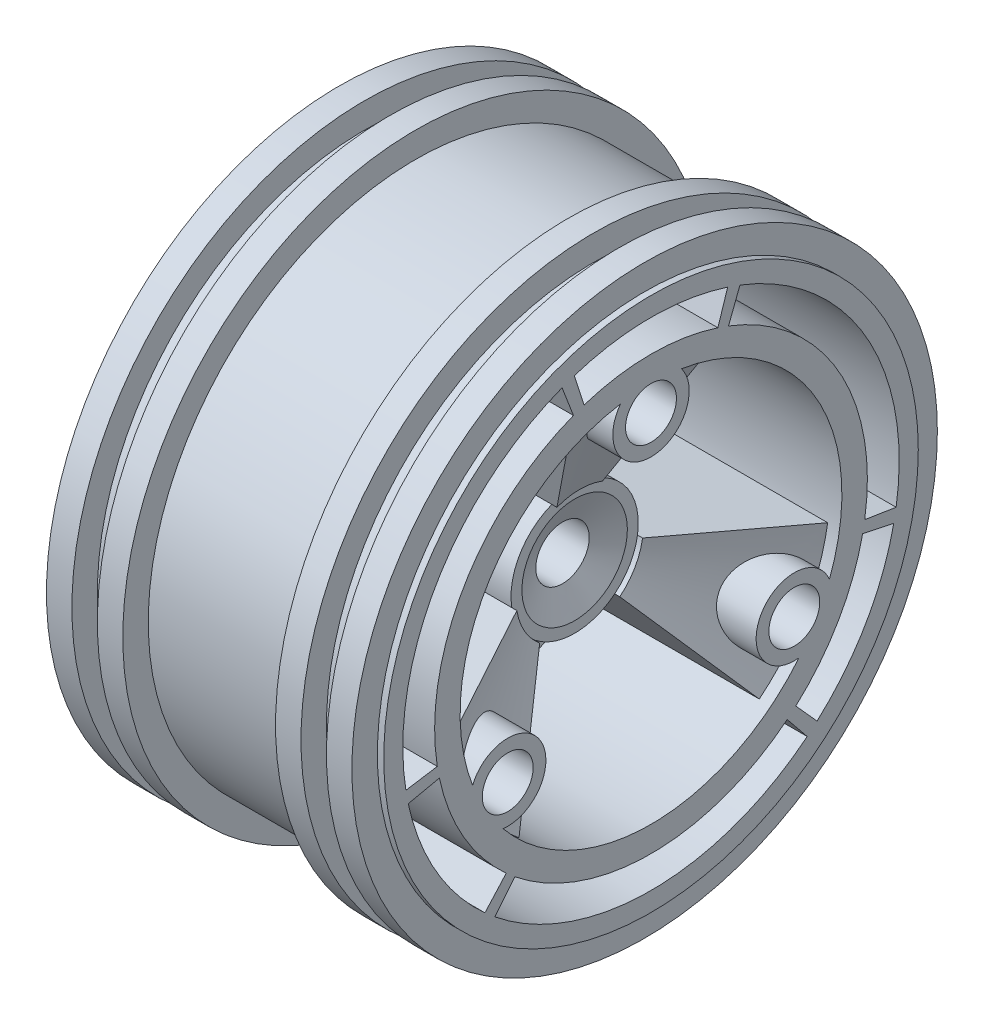
SolidWorks part; units mm, degrees
ref_plane "Plan de face" through (0, 0, 0) normal (0, 0, 1) x (1, 0, 0)
ref_plane "Plan de dessus" through (0, 0, 0) normal (0, 1, 0) x (1, 0, 0)
ref_plane "Plan de droite" through (0, 0, 0) normal (1, 0, 0) x (0, 0, -1)
sketch "Esquisse1" plane through (0, 0, 0) normal (0, 0, 1) x (1, 0, 0)
  line L0 (-6.5, -2) -> (5.5, -2)
  line L1 (-6.5, -2) -> (-6.5, -19)
  line L2 (12.5, -17) -> (5.5, -2)
  line L3 (0, 0) -> (-22.8628, 0) construction
  line L5 (-6.5, -19) -> (-12.5, -19)
  line L6 (12.5, -17) -> (12.5, -21)
  line L7 (-12.5, -19) -> (-12.5, -21)
  line L8 (-12, -23) -> (12, -23) construction
  line L9 (-19.4227, -21) -> (12.5, -21) construction
  line L10 (-12, -23) -> (-10, -23)
  line L11 (-10, -23) -> (-10, -21)
  line L12 (-10, -21) -> (-8, -21)
  line L13 (-8, -21) -> (-8, -23)
  line L14 (-8, -23) -> (-6, -23)
  line L15 (-6, -23) -> (-6, -21)
  line L16 (-6, -21) -> (6, -21)
  line L17 (6, -21) -> (6, -23)
  line L18 (6, -23) -> (8, -23)
  line L19 (8, -23) -> (8, -21)
  line L20 (8, -21) -> (10, -21)
  line L21 (10, -21) -> (10, -23)
  line L22 (10, -23) -> (12, -23)
  line L23 (-12.5, -21) -> (-12, -21)
  line L24 (-12, -21) -> (-12, -23)
  line L25 (12.5, -21) -> (12, -21)
  line L26 (12, -21) -> (12, -23)
  point P0 (0, 0)
  dimension "D1" = 2
  dimension "D2" = 12
  dimension "D3" = 5.5
  dimension "D4" = 23
  dimension "D5" = 23
  dimension "D6" = 15
  dimension "D7" = 6
  dimension "D8" = 4
  dimension "D9" = 25
  dimension "D10" = 2
  dimension "D11" = 0.5
  dimension "D12" = 2
  dimension "D13" = 4
  dimension "D14" = 2
  dimension "D15" = 0.5
  dimension "D16" = 4
  dimension "D17" = 6
  dimension "D18" = 6
revolve "Révolution1" add sketch "Esquisse1" angle 360 about L3
sketch "Esquisse2" plane through (-6.5, 0, 0) normal (-1, 0, 0) x (0, 0, 1)
  line L0 (0, 19) -> (0, 15) construction
  line L1 (-19, 0) -> (-15, 0) construction
  line L2 (-9.5263, 5.5) -> (-8.6603, 5) construction
  line L3 (-9.5263, -5.5) -> (-8.6603, -5) construction
  line L4 (-1.8187, 1.05) -> (1.8187, -1.05) construction
  line L5 (-2.1, 0) -> (5, 0) construction
  line L6 (-1.8187, -1.05) -> (1.8187, 1.05) construction
  line L7 (0, 5) -> (0, -2.1) construction
  line L8 (0, 11) -> (0, 10) construction
  line L9 (8.6603, -5) -> (9.5263, -5.5) construction
  line L10 (15, 0) -> (19, 0) construction
  line L11 (0, -10) -> (0, -11) construction
  line L12 (-5.1303, 14.0954) -> (0, 0) construction
  line L13 (5.1303, 14.0954) -> (0, 0) construction
  line L14 (5.1303, 14.0954) -> (1.7101, 4.6985)
  line L15 (-5.1303, 14.0954) -> (-1.7101, 4.6985)
  line L16 (0, 0) -> (-14.7721, -2.6047) construction
  line L17 (0, 0) -> (-9.6418, -11.4907) construction
  line L18 (0, 0) -> (14.7721, -2.6047) construction
  line L19 (0, 0) -> (9.6418, -11.4907) construction
  line L20 (-14.7721, -2.6047) -> (-4.924, -0.8682)
  line L21 (-9.6418, -11.4907) -> (-3.2139, -3.8302)
  line L22 (9.6418, -11.4907) -> (3.2139, -3.8302)
  line L23 (14.7721, -2.6047) -> (4.924, -0.8682)
  circle A0 centre (-11.2583, 6.5) radius 2
  circle A1 centre (0, 0) radius 2.1
  circle A2 centre (11.2583, -6.5) radius 2
  circle A3 centre (0, 0) radius 19 construction
  circle A4 centre (0, 0) radius 19 construction
  circle A5 centre (0, 13) radius 2
  circle A6 centre (0, -13) radius 2
  arc A7 (-2.3942, 14.8077) -> (-11.6267, 9.4773) centre (0, 0) ccw
  circle A8 centre (-11.2583, -6.5) radius 2
  circle A9 centre (11.2583, 6.5) radius 2
  circle A10 centre (0, 0) radius 5
  arc A11 (-2.3942, 14.8077) -> (2.3942, 14.8077) centre (0, 13) ccw
  arc A12 (11.6267, 9.4773) -> (14.0209, 5.3304) centre (11.2583, 6.5) ccw
  arc A13 (-14.0209, 5.3304) -> (-11.6267, 9.4773) centre (-11.2583, 6.5) ccw
  arc A14 (-11.6267, -9.4773) -> (-14.0209, -5.3304) centre (-11.2583, -6.5) ccw
  arc A15 (2.3942, -14.8077) -> (-2.3942, -14.8077) centre (0, -13) ccw
  arc A16 (14.0209, -5.3304) -> (11.6267, -9.4773) centre (11.2583, -6.5) ccw
  arc A17 (-14.0209, 5.3304) -> (-14.0209, -5.3304) centre (0, 0) ccw
  arc A18 (11.6267, 9.4773) -> (2.3942, 14.8077) centre (0, 0) ccw
  arc A19 (14.0209, -5.3304) -> (14.0209, 5.3304) centre (0, 0) ccw
  arc A20 (2.3942, -14.8077) -> (11.6267, -9.4773) centre (0, 0) ccw
  arc A21 (-11.6267, -9.4773) -> (-2.3942, -14.8077) centre (0, 0) ccw
  circle A22 centre (0, 0) radius 3
  circle M1 centre (0, 0) radius 19
  dimension "D1" = 4.2
  dimension "D2" = 4
  dimension "D3" = 4
  dimension "D8" = 4
  dimension "D9" = 4
  dimension "D10" = 4
  dimension "D11" = 4
  dimension "D16" = 10
  dimension "D17" = 6
  dimension "D18" = 6
  dimension "D19" = 6
  dimension "D20" = 6
  dimension "D21" = 6
  dimension "D22" = 6
  dimension "D29" = 6
  dimension "D4" = 13
  dimension "D5" = 13
  dimension "D6" = 30
  dimension "D7" = 60
  dimension "D12" = 13
  dimension "D13" = 13
  dimension "D14" = 13
  dimension "D15" = 13
  dimension "D23" = 20
  dimension "D24" = 40
  dimension "D25" = 20
  dimension "D26" = 40
  dimension "D27" = 20
  dimension "D28" = 40
extrude "Enlèv. mat.-Extru.1" cut sketch "Esquisse2" against normal blind 20 contours A0 region at (-6.5, 6.5, -11.2583)
extrude "Enlèv. mat.-Extru.2" cut sketch "Esquisse2<3>" against normal blind 20 contours A5 | A9 | A2 | A6 | A8 | A1 region at (-6.5, 0, 0) region at (-6.5, -6.5, 11.2583) region at (-6.5, 13, 0) region at (-6.5, -13, 0) region at (-6.5, -6.5, -11.2583) region at (-6.5, 6.5, 11.2583)
sketch "Esquisse2<3>" plane through (-6.5, 0, 0) normal (-1, 0, 0) x (0, 0, 1) same geometry as "Esquisse2"
extrude "Enlèv. mat.-Extru.3" cut sketch "Esquisse2<4>" against normal blind 11 contours L14 A18 A11 A7 L15 A10 | L22 A20 A16 A19 L23 A10 | A14 A21 L21 A10 L20 A17 region at (-6.5, 9.4701, 0) region at (-6.5, -4.7351, 8.2014) region at (-6.5, -4.7351, -8.2014)
sketch "Esquisse2<4>" plane through (-6.5, 0, 0) normal (-1, 0, 0) x (0, 0, 1) same geometry as "Esquisse2"
extrude "Enlèv. mat.-Extru.4" cut sketch "Esquisse2<6>" against normal blind 1 contours A10 A22 region at (-6.5, 2.7868, 3.9799)
sketch "Esquisse2<6>" plane through (-6.5, 0, 0) normal (-1, 0, 0) x (0, 0, 1) same geometry as "Esquisse2"
extrude "Enlèv. mat.-Extru.5" cut sketch "Esquisse2<7>" against normal blind 0.5 contours A13 A17 L20 A10 L15 A7 | L23 A19 A12 A18 L14 A10 | L21 A21 A15 A20 L22 A10 region at (-6.5, 4.6938, 8.1298) region at (-6.5, 4.6938, -8.1298) region at (-6.5, -9.3875, 0)
sketch "Esquisse2<7>" plane through (-6.5, 0, 0) normal (-1, 0, 0) x (0, 0, 1) same geometry as "Esquisse2"
extrude "Boss.-Extru.1" add sketch "Esquisse2<8>" against normal blind 19 contours A21 A14 A17 A13 A7 A11 A18 A12 A19 A16 A20 A15 A9 A8 A6 A5 A2 A0 M1 region at (-6.5, 0, -18.4626)
sketch "Esquisse2<8>" plane through (-6.5, 0, 0) normal (-1, 0, 0) x (0, 0, 1) same geometry as "Esquisse2"
sketch "Esquisse7" plane through (12.5, 0, 0) normal (1, 0, 0) x (0, 0, -1)
  line L0 (0, 15) -> (0, -15) construction
  line L1 (-4.5925, -1.9771) -> (14.8691, -1.9771) construction
  line L2 (-5.3755, 14.0037) -> (-1.1227, 2.9248) construction
  line L3 (0, 0) -> (1.0751, 2.8007) construction
  line L4 (-5.3755, 14.0037) -> (-1.1227, 2.9248)
  line L5 (5.3755, 14.0037) -> (1.7918, 4.6679)
  line L6 (-14.8153, -2.3465) -> (-4.9384, -0.7822) construction
  line L7 (0, 0) -> (-1.888, -2.3314) construction
  line L8 (9.4398, -11.6572) -> (1.888, -2.3314) construction
  line L9 (0, 0) -> (2.9631, -0.4693) construction
  line L10 (14.8153, -2.3465) -> (4.9384, -0.7822)
  line L11 (9.4398, -11.6572) -> (1.888, -2.3314)
  line L12 (1.888, -2.3314) -> (0, 0) construction
  line L13 (4.9384, -0.7822) -> (14.8153, -2.3465) construction
  line L14 (1.7918, 4.6679) -> (5.3755, 14.0037) construction
  line L15 (-1.0751, 2.8007) -> (0, 0) construction
  line L16 (-2.9631, -0.4693) -> (0, 0) construction
  line L17 (-3.1466, -3.8857) -> (-9.4398, -11.6572) construction
  line L18 (-14.8153, -2.3465) -> (-4.9384, -0.7822)
  line L19 (-9.4398, -11.6572) -> (-3.1466, -3.8857)
  circle A0 centre (0, 13) radius 2 construction
  circle A1 centre (0, -13) radius 2 construction
  arc A2 (2.3942, -14.8077) -> (-2.3942, -14.8077) centre (0, -13) ccw
  circle A4 centre (0, 0) radius 5
  circle A5 centre (0, 0) radius 3
  arc A6 (2.3942, -14.8077) -> (14.0209, 5.3304) centre (0, 0) ccw
  arc A7 (-14.0209, 5.3304) -> (-11.6267, 9.4773) centre (-11.2583, 6.5) ccw
  arc A8 (11.6267, 9.4773) -> (14.0209, 5.3304) centre (11.2583, 6.5) ccw
  arc A9 (-14.8153, -2.3465) -> (-2.3942, -14.8077) centre (0, 0) ccw
  arc A10 (11.6267, 9.4773) -> (-11.6267, 9.4773) centre (0, 0) ccw
  circle A11 centre (0, 0) radius 15
  arc M1 (-14.0209, 5.3304) -> (-11.6267, 9.4773) centre (-11.2583, 6.5) ccw
  arc M5 (11.6267, 9.4773) -> (14.0209, 5.3304) centre (11.2583, 6.5) ccw
  arc M9 (2.3942, -14.8077) -> (-2.3942, -14.8077) centre (0, -13) ccw
  dimension "D1" = 10
  dimension "D2" = 6
  dimension "D3" = 30
  dimension "D10" = 6
  dimension "D11" = 6
  dimension "D12" = 6
  dimension "D4" = 69
  dimension "D5" = 69
  dimension "D6" = 9
  dimension "D7" = 42
  dimension "D8" = 9
  dimension "D9" = 42
extrude "Enlèv. mat.-Extru.6" cut sketch "Esquisse7" against normal blind 15 contours A4 L19 L11 M9 | A4 L4 L18 M1 | A4 L10 L5 M5 region at (12.5, 4.7099, 8.1578) region at (12.5, 4.7099, -8.1578) region at (12.5, -9.4198, 0)
extrude "Enlèv. mat.-Extru.9" cut sketch "Esquisse7<5>" against normal blind 6 contours A4 A5 region at (12.5, 4.8586, 0)
sketch "Esquisse7<5>" plane through (12.5, 0, 0) normal (1, 0, 0) x (0, 0, -1) same geometry as "Esquisse7"
sketch "Esquisse13" plane through (12.5, 0, 0) normal (1, 0, 0) x (0, 0, -1)
  arc A0 (11.6267, 9.4773) -> (14.0209, 5.3304) centre (11.2583, 6.5) ccw
  arc A1 (-14.0209, 5.3304) -> (-11.6267, 9.4773) centre (-11.2583, 6.5) ccw
  arc A2 (2.3942, -14.8077) -> (-2.3942, -14.8077) centre (0, -13) ccw
  arc A3 (-11.6267, 9.4773) -> (-14.0209, 5.3304) centre (0, 0) ccw
  arc A4 (-2.3942, -14.8077) -> (2.3942, -14.8077) centre (0, 0) ccw
  arc A5 (14.0209, 5.3304) -> (11.6267, 9.4773) centre (0, 0) ccw
  dimension "D1" = 30
  dimension "D2" = 6
  dimension "D3" = 6
  dimension "D4" = 6
extrude "Enlèv. mat.-Extru.12" cut sketch "Esquisse13" against normal blind 14.5
sketch "Esquisse14" plane through (12.5, 0, 0) normal (1, 0, 0) x (0, 0, -1)
  line L0 (0, -17) -> (0, 15) construction
  line L1 (-14.8661, 0) -> (14.8661, 0) construction
  line L2 (6.0923, 15.8709) -> (6.9882, 18.2048)
  line L3 (-6.0923, 15.8709) -> (-6.9882, 18.2048)
  line L4 (-19.2599, -3.0505) -> (-16.7907, -2.6594)
  line L5 (-10.6984, -13.2115) -> (-12.2717, -15.1543)
  line L6 (12.2717, -15.1543) -> (10.6984, -13.2115)
  line L7 (16.7907, -2.6594) -> (19.2599, -3.0505)
  line L8 (5.2533, 16.168) -> (6.0258, 18.5456)
  line L9 (-6.0258, 18.5456) -> (-5.2533, 16.168)
  line L10 (-11.3752, -12.6335) -> (-13.048, -14.4913)
  line L11 (-16.6285, -3.5345) -> (-19.0739, -4.0543)
  line L13 (11.3752, -12.6335) -> (13.048, -14.4913)
  line L14 (16.6285, -3.5345) -> (19.0739, -4.0543)
  circle A1 centre (0, 13) radius 2 construction
  arc A5 (6.0258, 18.5456) -> (-6.0258, 18.5456) centre (0, 0) ccw
  arc A6 (5.2533, 16.168) -> (-5.2533, 16.168) centre (0, 0) ccw
  circle A7 centre (0, 0) radius 16
  arc A8 (-6.9882, 18.2048) -> (-19.2599, -3.0505) centre (0, 0) ccw
  arc A9 (-6.0923, 15.8709) -> (-16.7907, -2.6594) centre (0, 0) ccw
  arc A10 (-19.0739, -4.0543) -> (-13.048, -14.4913) centre (0, 0) ccw
  arc A11 (-16.6285, -3.5345) -> (-11.3752, -12.6335) centre (0, 0) ccw
  arc A12 (16.7907, -2.6594) -> (6.0923, 15.8709) centre (0, 0) ccw
  arc A13 (19.2599, -3.0505) -> (6.9882, 18.2048) centre (0, 0) ccw
  arc A14 (11.3752, -12.6335) -> (16.6285, -3.5345) centre (0, 0) ccw
  arc A15 (13.048, -14.4913) -> (19.0739, -4.0543) centre (0, 0) ccw
  arc A16 (-10.6984, -13.2115) -> (10.6984, -13.2115) centre (0, 0) ccw
  arc A17 (-12.2717, -15.1543) -> (12.2717, -15.1543) centre (0, 0) ccw
  dimension "D7" = 39
  dimension "D8" = 17
  dimension "D27" = 1
  dimension "D1" = 42
  dimension "D2" = 69
  dimension "D3" = 78
  dimension "D4" = 42
  dimension "D5" = 78
  dimension "D6" = 42
  dimension "D9" = 3
  dimension "D10" = 2.5
  dimension "D11" = 3
  dimension "D12" = 3
  dimension "D13" = 3
  dimension "D14" = 2.5
  dimension "D15" = 3
  dimension "D16" = 2.5
  dimension "D17" = 2.5
  dimension "D18" = 3
  dimension "D19" = 2.5
  dimension "D20" = 2.5
  dimension "D21" = 2.5
  dimension "D22" = 2.5
  dimension "D23" = 2.5
  dimension "D24" = 0.89
  dimension "D25" = 0.89
  dimension "D26" = 1.0209
extrude "Enlèv. mat.-Extru.13" cut sketch "Esquisse14" against normal blind 17 contours L8 A13 L9 A12 | L7 A13 L2 A12 | L13 A15 L14 A14 | A11 L11 A10 L10 | L3 A8 L4 A9 | A16 L6 A17 L5 region at (12.5, 16.9478, -6.7748) region at (12.5, 17.9793, 0) region at (12.5, -8.9897, 15.5706) region at (12.5, -8.9897, -15.5706)
